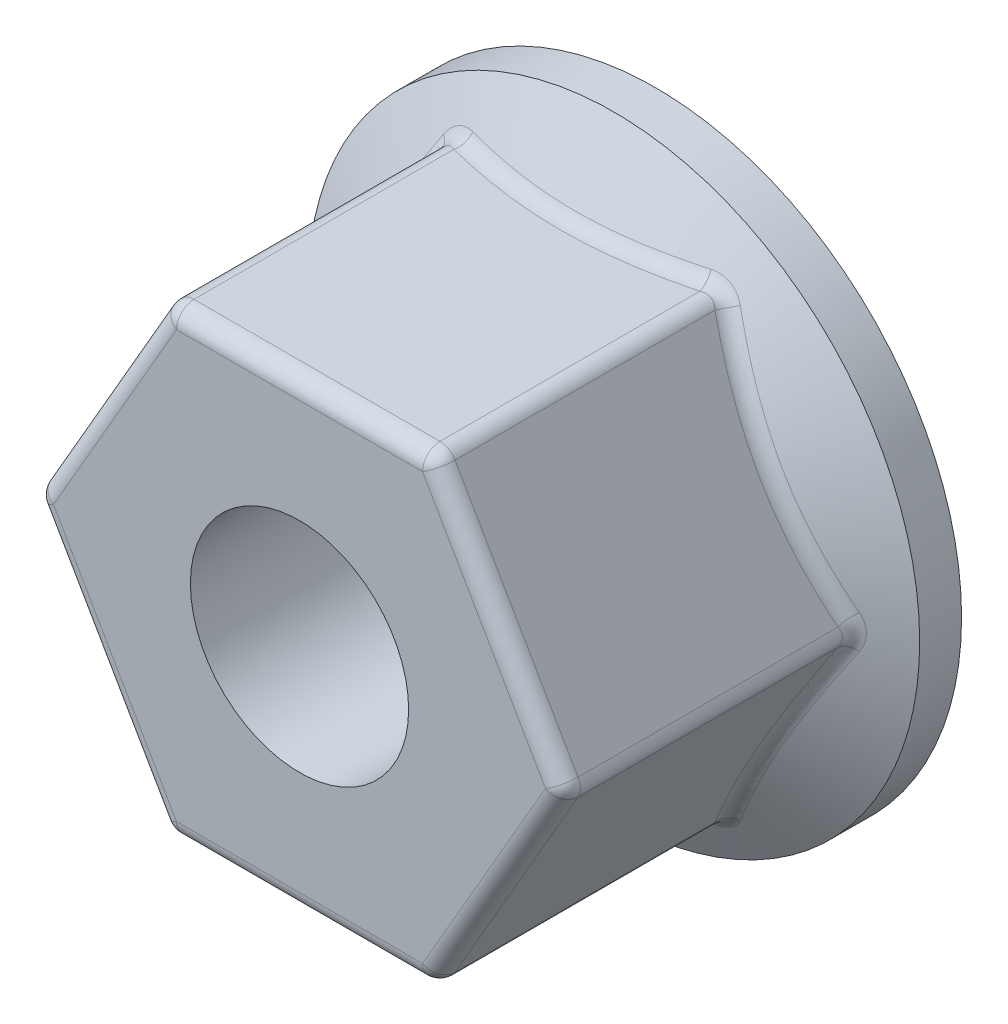
SolidWorks part; units mm, degrees
ref_plane "Front Plane" through (0, 0, 0) normal (0, 0, 1) x (1, 0, 0)
ref_plane "Top Plane" through (0, 0, 0) normal (0, 1, 0) x (1, 0, 0)
ref_plane "Right Plane" through (0, 0, 0) normal (1, 0, 0) x (0, 0, -1)
sketch "Sketch1" plane through (0, 0, 0) normal (0, 0, 1) x (1, 0, 0)
  circle A0 centre (0, 0) radius 11.1252
  dimension "D1" = 22.2504
extrude "Boss-Extrude1" add sketch "Sketch1" along normal blind 1.524
sketch "Sketch2" plane through (0, 0, 1.524) normal (0, 0, 1) x (1, 0, 0)
  line L1 (9.6787, 0) -> (4.8393, 8.382)
  line L2 (4.8393, 8.382) -> (-4.8393, 8.382)
  line L3 (-4.8393, 8.382) -> (-9.6787, 0)
  line L4 (-9.6787, 0) -> (-4.8393, -8.382)
  line L5 (-4.8393, -8.382) -> (4.8393, -8.382)
  line L6 (4.8393, -8.382) -> (9.6787, 0)
  circle A0 centre (0, 0) radius 8.382 construction
  dimension "D1" = 16.764
extrude "Boss-Extrude2" add sketch "Sketch2" along normal offset from surface (11.43 mm away) 12.954 up to face at (11.1252, 0, 0)
sketch "Sketch5" plane through (0, 0, 1.524) normal (0, 0, 1) x (1, 0, 0)
  circle A0 centre (0, 0) radius 11.1252
extrude "Boss-Extrude3" add sketch "Sketch5" along normal blind 1.905 draft 60
hole_wizard "3/8-16 Tapped Hole1" positions "Sketch3" profile "Sketch4" tap size "3/8-16" standard "ANSI Inch" end condition through all
sketch "Sketch3" plane through (0, 0, 12.954) normal (0, 0, 1) x (1, 0, 0)
  point P0 (0, 0)
cosmetic thread "Hole Thread1" parameters "D2"=9.525
sketch "Sketch4" plane through (0, 0, 12.954) normal (1, 0, 0) x (0, -1, 0)
  line L0 (0, 0) -> (0, 12.954)
  line L1 (0, 12.954) -> (3.9687, 12.954)
  line L2 (3.9687, 12.954) -> (3.9687, 0)
  line L5 (3.9687, 0) -> (0, 0)
  line L11 (0, -6.35) -> (0, 107.95) construction
  dimension "Thru Tap Drill Dia." = 7.9375
  dimension "Thru Tap Drill Depth" = 12.954
fillet "Fillet1" radius 0.635 18 edges at (4.8393, 8.382, 7.6566) (-4.8393, 8.382, 7.6566) (-9.6787, 0, 7.6566) (9.6787, 0, 7.6566) (4.8393, -8.382, 7.6566) (-4.8393, -8.382, 7.6566) (-7.259, 4.191, 12.954) (-7.087, 4.489, 3.1037) (7.259, 4.191, 12.954) (7.4311, 3.893, 3.1037) (0, 8.382, 12.954) (1.2715, 8.382, 3.0524) (7.259, -4.191, 12.954) (7.087, -4.489, 3.1037) (-7.259, -4.191, 12.954) (-7.4311, -3.893, 3.1037) (0, -8.382, 12.954) (1.2715, -8.382, 3.0524)
